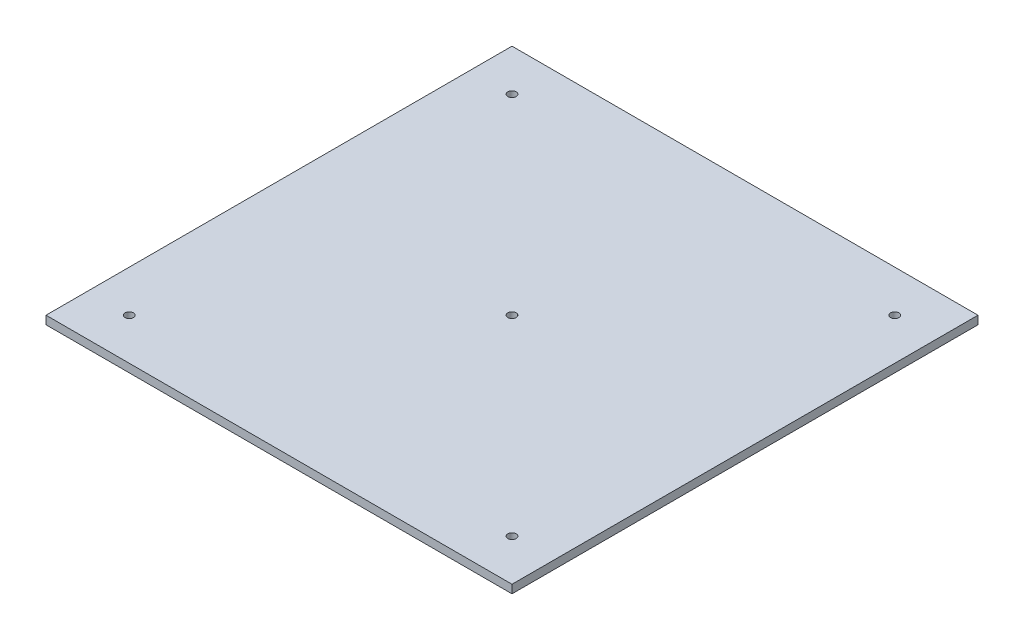
SolidWorks part; units mm, degrees
material "2014-T6"
ref_plane "Front Plane" through (0, 0, 0) normal (0, 0, 1) x (1, 0, 0)
ref_plane "Top Plane" through (0, 0, 0) normal (0, 1, 0) x (1, 0, 0)
ref_plane "Right Plane" through (0, 0, 0) normal (1, 0, 0) x (0, 0, -1)
sketch "Sketch1" plane through (0, 0, 0) normal (0, 1, 0) x (1, 0, 0)
  line L1 (-56, 56) -> (56, 56)
  line L2 (-56, 56) -> (-56, -56)
  line L3 (-56, -56) -> (56, -56)
  line L4 (56, 56) -> (56, -56)
  dimension "D1" = 112
  dimension "D2" = 112
  dimension "D3" = 56
  dimension "D4" = 56
extrude "Boss-Extrude1" add sketch "Sketch1" along normal blind 2
sketch "Sketch2" plane through (0, 2, 0) normal (0, 1, 0) x (1, 0, 0)
  line L0 (-56, -56) -> (56, -56) construction
  line L1 (-56, 56) -> (-56, -56) construction
  circle A0 centre (-46, -46) radius 1
  circle A1 centre (0, 0) radius 1
  dimension "D3" = 2
  dimension "D4" = 2
  dimension "D1" = 10
  dimension "D2" = 10
extrude "Cut-Extrude1" cut sketch "Sketch2" against normal blind 2
mirror "Mirror1" about plane through (0, 0, 0) normal (1, 0, 0) of "Cut-Extrude1" second plane through (0, 0, 0) second plane normal (0, 0, 1)
